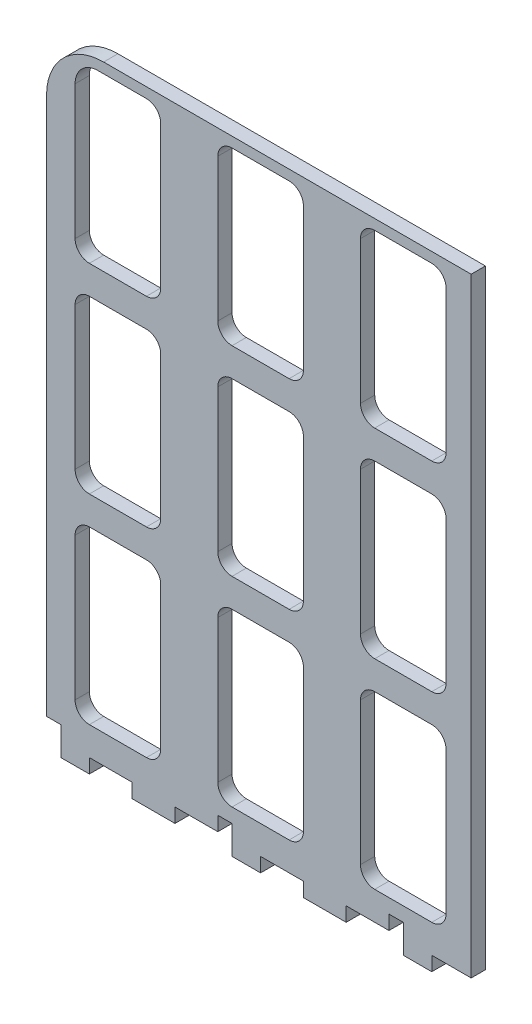
SolidWorks part; units mm, degrees
material "Balsa"
ref_plane "Front Plane" through (0, 0, 0) normal (0, 0, 1) x (1, 0, 0)
ref_plane "Top Plane" through (0, 0, 0) normal (0, 1, 0) x (1, 0, 0)
ref_plane "Right Plane" through (0, 0, 0) normal (1, 0, 0) x (0, 0, -1)
sketch "Sketch1" plane through (0, 0, 0) normal (0, 0, 1) x (1, 0, 0)
  line L1 (188.976, 0) -> (188.976, 271.272)
  line L2 (188.976, 271.272) -> (25.4, 271.272)
  line L4 (0, 0) -> (0, -6.35)
  line L6 (0, 0) -> (0, -6.35)
  line L7 (0, -6.35) -> (19.05, -6.35)
  line L8 (19.05, 0) -> (19.05, -6.35)
  line L10 (38.1, 0) -> (38.1, -6.35)
  line L11 (38.1, -6.35) -> (57.15, -6.35)
  line L12 (57.15, 0) -> (57.15, -6.35)
  line L14 (76.2, 0) -> (76.2, -6.35)
  line L15 (76.2, -6.35) -> (95.25, -6.35)
  line L16 (95.25, 0) -> (95.25, -6.35)
  line L18 (114.3, 0) -> (114.3, -6.35)
  line L19 (114.3, -6.35) -> (133.35, -6.35)
  line L20 (133.35, 0) -> (133.35, -6.35)
  line L22 (152.4, 0) -> (152.4, -6.35)
  line L23 (152.4, -6.35) -> (171.45, -6.35)
  line L24 (171.45, 0) -> (171.45, -6.35)
  line L25 (19.05, 0) -> (38.1, 0)
  line L26 (57.15, 0) -> (76.2, 0)
  line L27 (95.25, 0) -> (114.3, 0)
  line L28 (133.35, 0) -> (152.4, 0)
  line L29 (171.45, 0) -> (188.976, 0)
  line L30 (0, 245.872) -> (0, 0)
  line L31 (25.4, 271.272) -> (188.976, 271.272)
  line L32 (19.05, 0) -> (38.1, 0)
  line L33 (38.1, -6.35) -> (57.15, -6.35)
  line L34 (57.15, 0) -> (76.2, 0)
  arc A0 (25.4, 271.272) -> (0, 245.872) centre (25.4, 245.872) ccw
  point P8 (0, 271.272)
  point P11 (188.976, 271.272)
  dimension "D4" = 6.35
  dimension "D5" = 19.05
  dimension "D1" = 188.976
  dimension "D2" = 271.272
  dimension "D3" = 188.976
  dimension "D6" = 6.35
  dimension "D7" = 19.05
  dimension "D8" = 19.05
  dimension "D9" = 19.05
  dimension "D10" = 19.05
  dimension "D11" = 6.35
  dimension "D12" = 19.05
  dimension "D13" = 19.05
  dimension "D14" = 6.35
  dimension "D15" = 19.05
  dimension "D16" = 19.05
  dimension "D17" = 6.35
  dimension "D18" = 245.872
  dimension "D19" = 163.576
  dimension "D20" = 271.272
  dimension "D21" = 6.35
  dimension "D22" = 6.35
  dimension "D23" = 6.35
extrude "Boss-Extrude1" add sketch "Sketch1" along normal blind 6.35 contours L2 A0 L30 L4 L7 L8 L25 L10 L11 L12 L26 L14 L15 L16 L27 L18 L19 L20 L28 L22 L23 L24 L29 L1 region at (94.6232, 133.6652, 0)
sketch "Sketch2" plane through (0, 0, 6.35) normal (0, 0, 1) x (1, 0, 0)
  line L0 (0, 245.872) -> (0, -6.35) construction
  line L5 (44.45, 266.7) -> (22.86, 266.7)
  line L38 (76.2, 19.05) -> (76.2, 82.55)
  line L39 (19.05, 12.7) -> (44.45, 12.7)
  line L40 (188.976, 271.272) -> (25.4, 271.272) construction
  line L68 (12.7, 19.05) -> (12.7, 82.55)
  line L69 (19.05, 88.9) -> (44.45, 88.9)
  line L70 (50.8, 19.05) -> (50.8, 82.55)
  line L71 (82.55, 12.7) -> (107.95, 12.7)
  line L72 (114.3, 19.05) -> (114.3, 82.55)
  line L73 (82.55, 88.9) -> (107.95, 88.9)
  line L74 (139.7, 19.05) -> (139.7, 82.55)
  line L75 (146.05, 12.7) -> (171.45, 12.7)
  line L76 (177.8, 19.05) -> (177.8, 82.55)
  line L77 (146.05, 88.9) -> (171.45, 88.9)
  line L78 (76.2, 107.95) -> (76.2, 171.45)
  line L79 (82.55, 101.6) -> (107.95, 101.6)
  line L80 (114.3, 107.95) -> (114.3, 171.45)
  line L81 (82.55, 177.8) -> (107.95, 177.8)
  line L82 (139.7, 107.95) -> (139.7, 171.45)
  line L83 (146.05, 101.6) -> (171.45, 101.6)
  line L84 (177.8, 107.95) -> (177.8, 171.45)
  line L85 (146.05, 177.8) -> (171.45, 177.8)
  line L86 (76.2, 196.85) -> (76.2, 260.35)
  line L87 (82.55, 190.5) -> (107.95, 190.5)
  line L88 (114.3, 196.85) -> (114.3, 260.35)
  line L89 (82.55, 266.7) -> (107.95, 266.7)
  line L90 (139.7, 196.85) -> (139.7, 260.35)
  line L91 (146.05, 190.5) -> (171.45, 190.5)
  line L92 (177.8, 196.85) -> (177.8, 260.35)
  line L93 (146.05, 266.7) -> (171.45, 266.7)
  line L94 (12.7, 107.95) -> (12.7, 171.45)
  line L95 (19.05, 101.6) -> (44.45, 101.6)
  line L96 (50.8, 107.95) -> (50.8, 171.45)
  line L97 (19.05, 177.8) -> (44.45, 177.8)
  line L98 (12.7, 196.85) -> (12.7, 256.54)
  line L99 (19.05, 190.5) -> (44.45, 190.5)
  line L100 (50.8, 196.85) -> (50.8, 260.35)
  line L104 (19.05, 266.7) -> (44.45, 266.7) [skipped]
  arc A0 (139.7, 19.05) -> (146.05, 12.7) centre (146.05, 19.05) ccw
  arc A1 (171.45, 12.7) -> (177.8, 19.05) centre (171.45, 19.05) ccw
  arc A22 (177.8, 82.55) -> (171.45, 88.9) centre (171.45, 82.55) ccw
  arc A23 (139.7, 82.55) -> (146.05, 88.9) centre (146.05, 82.55) cw
  arc A24 (76.2, 82.55) -> (82.55, 88.9) centre (82.55, 82.55) cw
  arc A25 (114.3, 82.55) -> (107.95, 88.9) centre (107.95, 82.55) ccw
  arc A26 (107.95, 12.7) -> (114.3, 19.05) centre (107.95, 19.05) ccw
  arc A27 (76.2, 19.05) -> (82.55, 12.7) centre (82.55, 19.05) ccw
  arc A28 (44.45, 12.7) -> (50.8, 19.05) centre (44.45, 19.05) ccw
  arc A29 (44.45, 88.9) -> (50.8, 82.55) centre (44.45, 82.55) cw
  arc A30 (12.7, 82.55) -> (19.05, 88.9) centre (19.05, 82.55) cw
  arc A31 (19.05, 12.7) -> (12.7, 19.05) centre (19.05, 19.05) cw
  arc A32 (12.7, 107.95) -> (19.05, 101.6) centre (19.05, 107.95) ccw
  arc A33 (12.7, 171.45) -> (19.05, 177.8) centre (19.05, 171.45) cw
  arc A34 (50.8, 171.45) -> (44.45, 177.8) centre (44.45, 171.45) ccw
  arc A35 (44.45, 101.6) -> (50.8, 107.95) centre (44.45, 107.95) ccw
  arc A36 (76.2, 107.95) -> (82.55, 101.6) centre (82.55, 107.95) ccw
  arc A37 (76.2, 171.45) -> (82.55, 177.8) centre (82.55, 171.45) cw
  arc A38 (114.3, 171.45) -> (107.95, 177.8) centre (107.95, 171.45) ccw
  arc A39 (107.95, 101.6) -> (114.3, 107.95) centre (107.95, 107.95) ccw
  arc A40 (139.7, 107.95) -> (146.05, 101.6) centre (146.05, 107.95) ccw
  arc A41 (171.45, 101.6) -> (177.8, 107.95) centre (171.45, 107.95) ccw
  arc A42 (139.7, 171.45) -> (146.05, 177.8) centre (146.05, 171.45) cw
  arc A43 (177.8, 171.45) -> (171.45, 177.8) centre (171.45, 171.45) ccw
  arc A44 (177.8, 260.35) -> (171.45, 266.7) centre (171.45, 260.35) ccw
  arc A45 (171.45, 190.5) -> (177.8, 196.85) centre (171.45, 196.85) ccw
  arc A46 (139.7, 196.85) -> (146.05, 190.5) centre (146.05, 196.85) ccw
  arc A47 (139.7, 260.35) -> (146.05, 266.7) centre (146.05, 260.35) cw
  arc A48 (76.2, 260.35) -> (82.55, 266.7) centre (82.55, 260.35) cw
  arc A49 (114.3, 260.35) -> (107.95, 266.7) centre (107.95, 260.35) ccw
  arc A50 (107.95, 190.5) -> (114.3, 196.85) centre (107.95, 196.85) ccw
  arc A51 (76.2, 196.85) -> (82.55, 190.5) centre (82.55, 196.85) ccw
  arc A52 (12.7, 196.85) -> (19.05, 190.5) centre (19.05, 196.85) ccw
  arc A53 (44.45, 190.5) -> (50.8, 196.85) centre (44.45, 196.85) ccw
  arc A54 (50.8, 260.35) -> (44.45, 266.7) centre (44.45, 260.35) ccw
  arc A56 (22.86, 266.7) -> (12.7, 256.54) centre (22.86, 256.54) ccw
  point P88 (50.8, 12.7)
  point P93 (12.7, 88.9)
  point P96 (12.7, 12.7)
  dimension "D7" = 6.35
  dimension "D12" = 4.572
  dimension "D11" = 10.16
  dimension "D1" = 76.2
  dimension "D2" = 38.1
  dimension "D3" = 3
  dimension "D4" = 3
  dimension "D5" = 12.7
  dimension "D6" = 12.7
  dimension "D8" = 25.4
  dimension "D9" = 12.7
  dimension "D10" = 12.7
extrude "Cut-Extrude1" cut sketch "Sketch2" against normal through all
sketch "Sketch3" plane through (0, 0, 6.35) normal (0, 0, 1) x (1, 0, 0)
  line L1 (0, -6.35) -> (6.35, -6.35)
  line L2 (0, -6.35) -> (0, 6.35)
  line L3 (0, 6.35) -> (6.35, 6.35)
  line L4 (6.35, -6.35) -> (6.35, 6.35)
  line L5 (76.2, -6.35) -> (82.55, -6.35)
  line L6 (76.2, -6.35) -> (76.2, 6.35)
  line L7 (76.2, 6.35) -> (82.55, 6.35)
  line L8 (82.55, -6.35) -> (82.55, 6.35)
  line L9 (152.4, -6.35) -> (158.75, -6.35)
  line L10 (152.4, -6.35) -> (152.4, 6.35)
  line L11 (152.4, 6.35) -> (158.75, 6.35)
  line L12 (158.75, -6.35) -> (158.75, 6.35)
  dimension "D1" = 6.35
  dimension "D2" = 12.7
  dimension "D3" = 6.35
  dimension "D4" = 12.7
  dimension "D5" = 12.7
  dimension "D6" = 6.35
extrude "Cut-Extrude2" cut sketch "Sketch3" against normal through all
